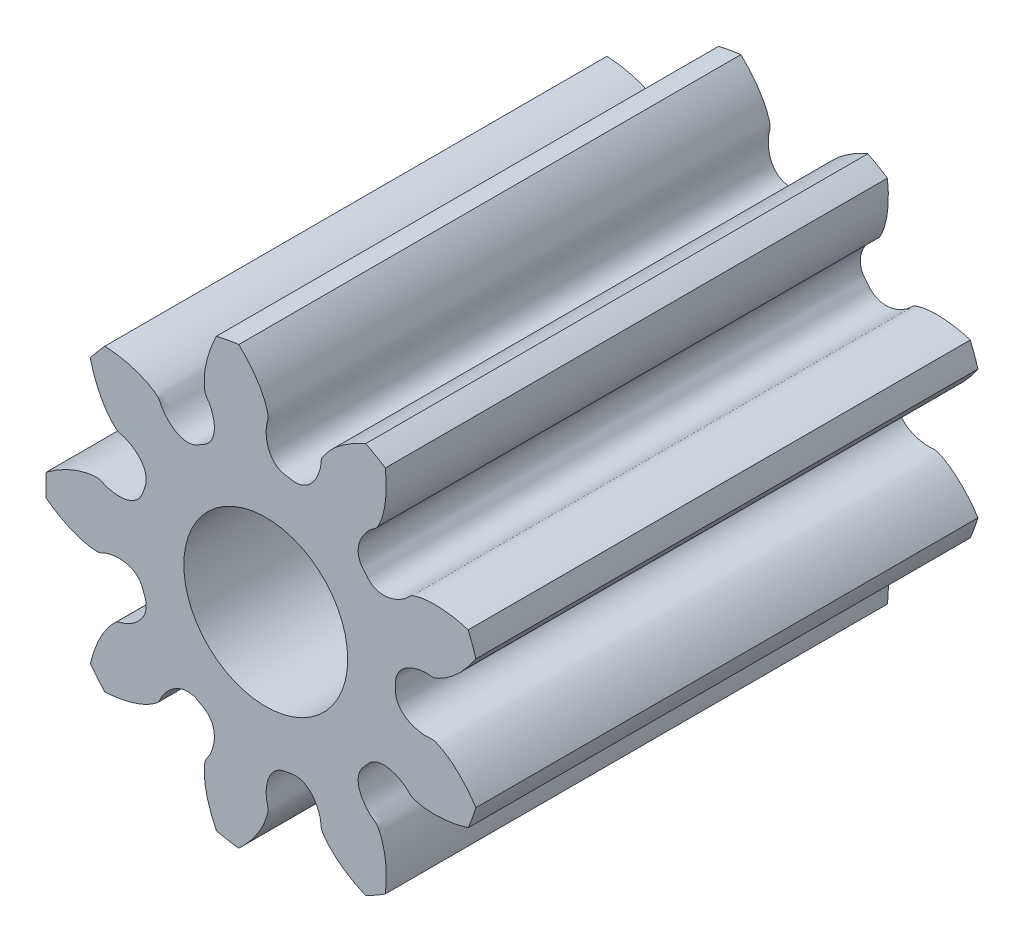
SolidWorks part; units mm, degrees
ref_plane "Front Plane" through (0, 0, 0) normal (0, 0, 1) x (1, 0, 0)
ref_plane "Top Plane" through (0, 0, 0) normal (0, 1, 0) x (1, 0, 0)
ref_plane "Right Plane" through (0, 0, 0) normal (1, 0, 0) x (0, 0, -1)
ref_axis "Axis1" through (0, 0, 55) along (0, 0, -1)
sketch "SketchRevolveSpurPinion" plane through (0, 0, 0) normal (1, 0, 0) x (0, 0, -1)
  line L0 (0, 0) -> (1, 0) construction
  line L1 (-1.225, 0) -> (-1.225, 1.0725)
  line L2 (-1.225, 1.0725) -> (1.225, 1.0725)
  line L3 (1.225, 1.0725) -> (1.225, 0)
  line L4 (1.225, 0) -> (-1.225, 0)
  dimension "Side1" = 1.225
  dimension "OutsideRadius" = 1.0725
  dimension "Side2" = 1.225
revolve "SpurPinion" add sketch "SketchRevolveSpurPinion" angle 360 about L0
sketch "SketchToothSpurPinion" plane through (0, 0, 0) normal (0, 0, 1) x (1, 0, 0)
  arc A0 (1.0322, 0.3252) -> (1.0322, -0.3252) centre (0, 0) cw
  spline S0 degree 3 poles (1.0322, -0.3252) (1.0222, -0.3092) (1.0066, -0.2864) (0.9845, -0.2583) (0.9685, -0.2397) (0.9527, -0.2228) (0.9373, -0.2077) (0.9224, -0.1942) (0.908, -0.1823) (0.8944, -0.1719) (0.8815, -0.163) (0.8696, -0.1555) (0.8586, -0.1491) (0.8487, -0.144) (0.8368, -0.1385) (0.8143, -0.1282) (0.7894, -0.135) (0.7688, -0.1328) (0.76, -0.1318) (0.7514, -0.1305) (0.743, -0.1288) (0.7348, -0.1269) (0.7269, -0.1247) (0.7191, -0.1222) (0.7115, -0.1194) (0.7042, -0.1163) (0.6971, -0.1128) (0.6902, -0.109) (0.6835, -0.1049) (0.6771, -0.1004) (0.671, -0.0955) (0.6651, -0.0902) (0.6595, -0.0845) (0.6543, -0.0783) (0.6496, -0.0717) (0.6452, -0.0646) (0.6415, -0.057) (0.6383, -0.0489) (0.6359, -0.0405) (0.6343, -0.0317) (0.6336, -0.0238) (0.6334, -0.0132) (0.634, 0) (0.6334, 0.0132) (0.6336, 0.0238) (0.6343, 0.0317) (0.6359, 0.0405) (0.6383, 0.0489) (0.6415, 0.057) (0.6452, 0.0646) (0.6496, 0.0717) (0.6543, 0.0783) (0.6595, 0.0845) (0.6651, 0.0902) (0.671, 0.0955) (0.6771, 0.1004) (0.6835, 0.1049) (0.6902, 0.109) (0.6971, 0.1128) (0.7042, 0.1163) (0.7115, 0.1194) (0.7191, 0.1222) (0.7269, 0.1247) (0.7348, 0.1269) (0.743, 0.1288) (0.7514, 0.1305) (0.76, 0.1318) (0.7688, 0.1328) (0.7894, 0.135) (0.8143, 0.1282) (0.8368, 0.1385) (0.8487, 0.144) (0.8586, 0.1491) (0.8696, 0.1555) (0.8815, 0.163) (0.8944, 0.1719) (0.908, 0.1823) (0.9224, 0.1942) (0.9373, 0.2077) (0.9527, 0.2228) (0.9685, 0.2397) (0.9845, 0.2583) (1.0066, 0.2864) (1.0222, 0.3092) (1.0322, 0.3252) knots 0 0 0 0 0.050891 0.074328 0.096425 0.117184 0.136602 0.154682 0.171423 0.186824 0.200886 0.213609 0.224992 0.235037 0.243742 0.260393 0.300254 0.308376 0.316344 0.324165 0.331849 0.339404 0.346842 0.354175 0.361415 0.368578 0.375679 0.382737 0.389771 0.396802 0.403852 0.410943 0.418101 0.425345 0.432698 0.440175 0.447788 0.455539 0.463422 0.471421 0.479511 0.484758 0.5 0.515242 0.520489 0.528579 0.536578 0.544461 0.552212 0.559825 0.567302 0.574655 0.581899 0.589057 0.596148 0.603198 0.610229 0.617263 0.624321 0.631422 0.638585 0.645825 0.653158 0.660596 0.668151 0.675835 0.683656 0.691624 0.699746 0.739607 0.756258 0.764963 0.775008 0.786391 0.799114 0.813176 0.828577 0.845318 0.863398 0.882816 0.903575 0.925672 0.949109 1 1 1 1
extrude "ToothExtrudeCutSpurPinion" cut sketch "SketchToothSpurPinion" against normal blind 9.525 and the other way blind 9.525
pattern_circular "PatternSpurPinion" count 9 every 40 about axis through (0, 0, 55) along (0, 0, -1) of "ToothExtrudeCutSpurPinion"
sketch "BoreRevolveSketch" plane through (0, 0, 0) normal (1, 0, 0) x (0, 0, -1)
  line L0 (0, 0) -> (1, 0) construction
  line L1 (-9.525, 0) -> (9.525, 0)
  line L2 (9.525, 0) -> (9.525, 6.35)
  line L3 (9.525, 6.35) -> (-9.525, 6.35)
  line L4 (-9.525, 6.35) -> (-9.525, 0)
  dimension "BoreSide1" = 9.525
  dimension "TaperSide1" = 6.35
  dimension "BoreSide2" = 9.525
  dimension "TaperSide2" = 6.35
sketch "AuxiliarySketchSpurPinion" plane through (0, 0, 0) normal (0, 0, 1) x (1, 0, 0)
  circle A0 centre (0, 0) radius 0.8775 construction
  circle A1 centre (0, 0) radius 0.8246 construction
  circle A2 centre (0, 0) radius 0.8775 construction
  circle A3 centre (0, 0) radius 1.0725 construction
  circle A4 centre (0, 0) radius 0.6337 construction
  dimension "PitchDiameter" = 1.755
  dimension "BaseDiameter" = 1.6492
  dimension "FormDiameter" = 1.7549
  dimension "MajorDiameter" = 2.145
  dimension "MinorDiameter" = 1.2675
sketch "Sketch5" plane through (0, 0, 1.225) normal (0, 0, 1) x (1, 0, 0)
  circle A0 centre (0, 0) radius 0.4
  dimension "D1" = 0.8
extrude "Cut-Extrude2" cut sketch "Sketch5" against normal blind 10
